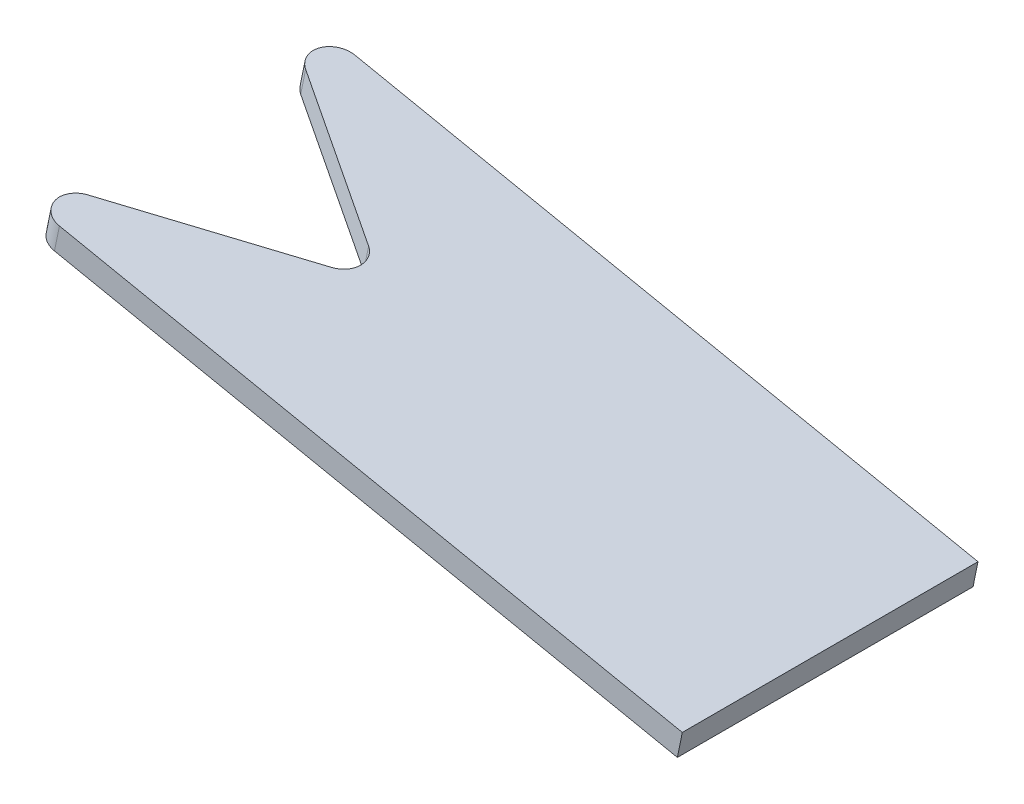
SolidWorks part; units mm, degrees
material "Balsa"
ref_plane "Front Plane" through (0, 0, 0) normal (0, 0, 1) x (1, 0, 0)
ref_plane "Top Plane" through (0, 0, 0) normal (0, 1, 0) x (1, 0, 0)
ref_plane "Right Plane" through (0, 0, 0) normal (1, 0, 0) x (0, 0, -1)
sketch "Sketch1" plane through (0, 0, 0) normal (0, 0, 1) x (1, 0, 0)
  line L0 (0, 0) -> (-391.9184, 80)
  line L1 (-391.9184, 80) -> (-388.9184, 94.6969)
  line L2 (0, 0) -> (3, 14.6969)
  line L3 (3, 14.6969) -> (-388.9184, 94.6969)
  point P2 (-240.05, 49)
  point P6 (-269.4439, 55)
  dimension "D1" = 80
  dimension "D2" = 400
  dimension "D3" = 30
extrude "Boss-Extrude3" add sketch "Sketch1" along normal blind 180
sketch "Sketch4" plane through (3, 14.6969, 0) normal (0.2, 0.9798, 0) x (0.9798, -0.2, 0)
  line L0 (-400, -20) -> (-278.7564, -90)
  line L1 (-400, -180) -> (-400, 0) construction
  line L2 (-278.7564, -90) -> (-400, -160)
  line L3 (-400, -20) -> (-400, -160)
  dimension "D1" = 140
  dimension "D2" = 140
extrude "Cut-Extrude1" cut sketch "Sketch4" against normal blind 180
fillet "Fillet1" radius 13 4 edges at (-390.4184, 87.3485, 0) (-390.4184, 87.3485, 20) (-390.4184, 87.3485, 180) (-390.4184, 87.3485, 160)
fillet "Fillet2" radius 13 1 edges at (-271.6244, 63.0998, 90)
other "Bounding Box"
ref_plane "Default Plane" through (-388.916, 94.6964, 0) normal (0, 0, 1) x (1, 0, 0)
